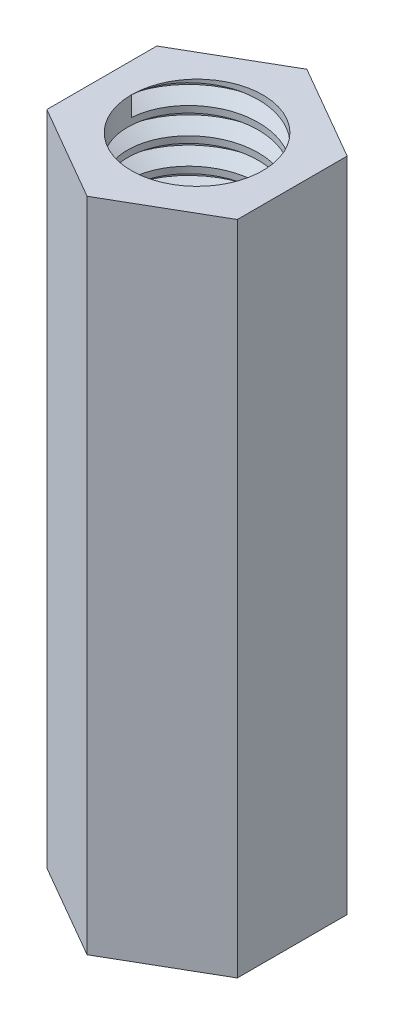
SolidWorks part; units mm, degrees
ref_plane "Front Plane" through (0, 0, 0) normal (0, 0, 1) x (1, 0, 0)
ref_plane "Top Plane" through (0, 0, 0) normal (0, 1, 0) x (1, 0, 0)
ref_plane "Right Plane" through (0, 0, 0) normal (1, 0, 0) x (0, 0, -1)
sketch "Sketch1" plane through (0, 0, 0) normal (0, 1, 0) x (1, 0, 0)
  line L0 (13.7368, -0.7955) -> (15.1868, 0.0416)
  line L1 (15.1868, 0.0416) -> (15.1868, 1.7136)
  line L2 (15.1868, 1.7136) -> (13.7348, 2.5519)
  line L3 (13.7348, 2.5519) -> (12.2868, 1.7159)
  line L4 (12.2868, 1.7159) -> (12.2868, 0.0416)
  line L5 (12.2868, 0.0416) -> (13.7368, -0.7955)
  dimension "D1" = 2.9
  dimension "D2" = 60
  dimension "D3" = 120
  dimension "D4" = 120
  dimension "D5" = 2.9
  dimension "D6" = 1.672
  dimension "D7" = 1.6743
extrude "Boss-Extrude1" add sketch "Sketch1" along normal blind 10
sketch "Sketch2" plane through (0, 10, 0) normal (0, 1, 0) x (1, 0, 0)
  circle A0 centre (13.7368, 0.8788) radius 1
  dimension "D1" = 2
extrude "Cut-Extrude1" cut sketch "Sketch2" against normal blind 10
thread "Thread1" pitch 0.4 method cut profile "Thread Profile1" start angle 0, offset 0, length 10, pitch 0.4, diameter 2
ref_plane "Plane1" through (12.7368, 10, -0.8788) normal (0, 0, 1) x (-1, 0, 0)
sketch "Thread Profile1" plane through (12.7368, 10, -0.8788) normal (0, 0, 1) x (-1, 0, 0)
  line L0 (0, 0) -> (0, 0.4) construction
  line L1 (0, 0) -> (0.2165, 0.125)
  line L2 (0.2165, 0.125) -> (0.2165, 0.175)
  line L3 (0.2165, 0.175) -> (0, 0.3)
  line L4 (0.2165, 0.15) -> (0, 0.15) construction
  line L11 (0, 0) -> (0, 0.3)
  point P2 (0, 0)
  dimension "Pitch" = 0.4
  dimension "Profile_Angle" = 60
  dimension "Profile_Land" = 0.05
  dimension "Profile_Height" = 0.2165
